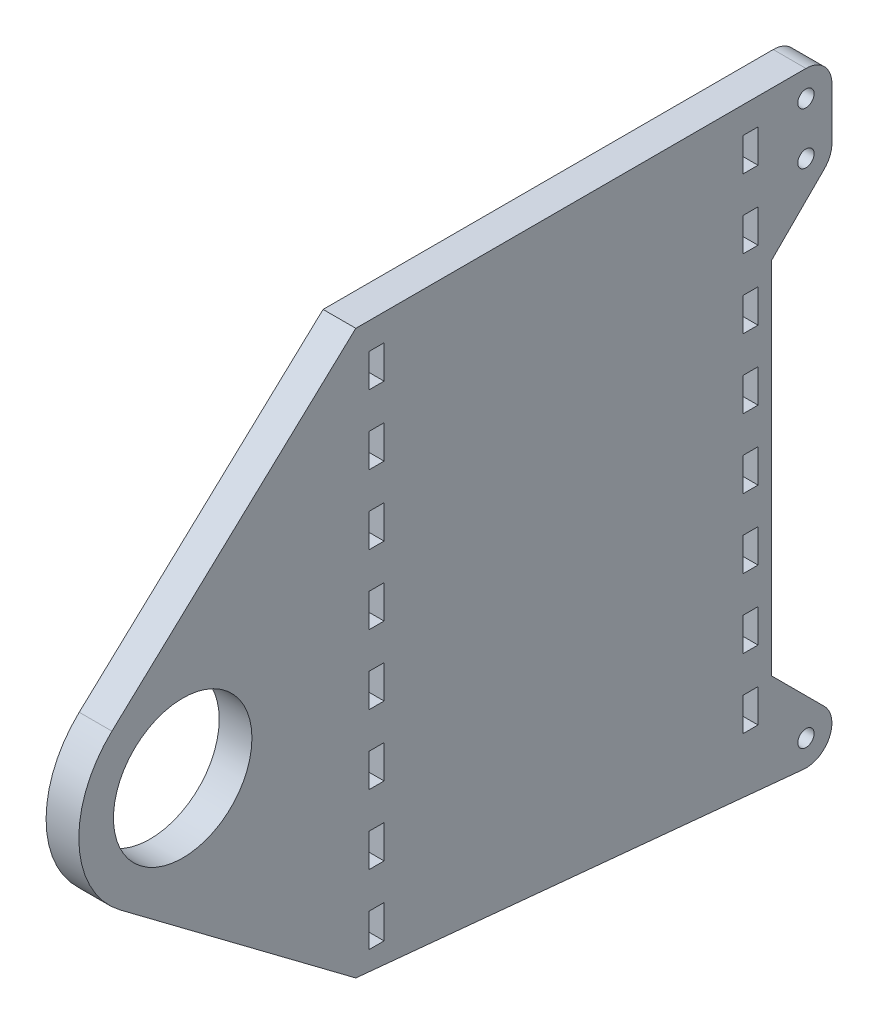
SolidWorks part; units mm, degrees
ref_plane "Front Plane" through (0, 0, 0) normal (0, 0, 1) x (1, 0, 0)
ref_plane "Top Plane" through (0, 0, 0) normal (0, 1, 0) x (1, 0, 0)
ref_plane "Right Plane" through (0, 0, 0) normal (1, 0, 0) x (0, 0, -1)
sketch "PlateGeometry" plane through (0, 0, 0) normal (1, 0, 0) x (0, 0, -1)
  line L1 (-38.1, -76.2) -> (38.1, -76.2) construction
  line L2 (-38.1, -76.2) -> (-38.1, 76.2) construction
  line L3 (-38.1, 76.2) -> (38.1, 76.2) construction
  line L4 (38.1, -76.2) -> (38.1, 76.2) construction
  line L5 (-38.1, -76.2) -> (38.1, 76.2) construction
  line L6 (-38.1, 76.2) -> (38.1, -76.2) construction
  line L11 (31.75, 76.2) -> (-31.75, 76.2) construction
  line L12 (31.75, 76.2) -> (31.75, -76.2) construction
  line L13 (31.75, -76.2) -> (-31.75, -76.2) construction
  line L14 (-31.75, 76.2) -> (-31.75, -76.2) construction
  line L15 (31.75, 76.2) -> (-31.75, -76.2) construction
  line L16 (31.75, -76.2) -> (-31.75, 76.2) construction
  point P0 (0, 0)
  point P9 (0, 0)
  line B0 (-35.7923, -66.6761) -> (-32.7923, -66.6739)
  line B1 (-35.7923, -66.6761) -> (-35.7877, -73.0261)
  line B2 (-35.7877, -73.0261) -> (-32.7877, -73.0239)
  line B3 (-32.7923, -66.6739) -> (-32.7877, -73.0239)
  line B4 (-35.7923, -66.6761) -> (-32.7877, -73.0239) construction
  line B5 (-35.7877, -73.0261) -> (-32.7923, -66.6739) construction
  line B6 (-35.7923, -53.9761) -> (-32.7923, -53.9739)
  line B7 (-35.7923, -53.9761) -> (-35.7877, -60.3261)
  line B8 (-35.7877, -60.3261) -> (-32.7877, -60.3239)
  line B9 (-32.7923, -53.9739) -> (-32.7877, -60.3239)
  line B10 (-35.7877, -60.3261) -> (-32.7923, -53.9739) construction
  line B11 (-35.7923, -41.2761) -> (-32.7923, -41.2739)
  line B12 (-35.7923, -41.2761) -> (-35.7877, -47.6261)
  line B13 (-35.7877, -47.6261) -> (-32.7877, -47.6239)
  line B14 (-32.7923, -41.2739) -> (-32.7877, -47.6239)
  line B15 (-35.7923, -41.2761) -> (-32.7877, -47.6239) construction
  line B16 (-35.7877, -47.6261) -> (-32.7923, -41.2739) construction
  line B17 (-35.7923, -28.5761) -> (-32.7923, -28.5739)
  line B18 (-35.7877, -34.9261) -> (-32.7877, -34.9239)
  line B19 (-32.7923, -28.5739) -> (-32.7877, -34.9239)
  line B20 (-35.7923, -15.8761) -> (-35.7877, -22.2261)
  line B21 (-32.7923, -15.8739) -> (-32.7877, -22.2239)
  line B22 (-35.7923, 9.5239) -> (-32.7923, 9.5261)
  line B23 (-32.7923, 9.5261) -> (-32.7877, 3.1761)
  line B24 (-35.7923, 9.5239) -> (-32.7877, 3.1761) construction
  line B25 (-35.7923, 22.2239) -> (-35.7877, 15.8739)
  line B26 (-35.7923, 34.9239) -> (-35.7877, 28.5739)
  line B27 (-35.7923, 47.6239) -> (-35.7877, 41.2739)
  line B28 (-35.7877, 41.2739) -> (-32.7923, 47.6261) construction
  line B29 (32.7886, -66.6757) -> (32.7914, -73.0257)
  line B30 (32.7914, -73.0257) -> (35.7914, -73.0243)
  line B31 (35.7886, -66.6743) -> (35.7914, -73.0243)
  line B32 (32.7886, -66.6757) -> (35.7914, -73.0243) construction
  line B33 (32.7914, -73.0257) -> (35.7886, -66.6743) construction
  line B34 (32.7886, -53.9757) -> (35.7886, -53.9743)
  line B35 (35.7886, -53.9743) -> (35.7914, -60.3243)
  line B36 (32.7914, -47.6257) -> (35.7914, -47.6243)
  line B37 (35.7886, -41.2743) -> (35.7914, -47.6243)
  line B38 (32.7886, -41.2757) -> (35.7914, -47.6243) construction
  line B39 (32.7886, -28.5757) -> (35.7914, -34.9243) construction
  line B40 (32.7886, -15.8757) -> (32.7914, -22.2257)
  line B41 (32.7886, -3.1757) -> (35.7914, -9.5243) construction
  line B42 (32.7914, -9.5257) -> (35.7886, -3.1743) construction
  line B43 (32.7886, 9.5243) -> (35.7886, 9.5257)
  line B44 (32.7886, 9.5243) -> (32.7914, 3.1743)
  line B45 (32.7914, 3.1743) -> (35.7914, 3.1757)
  line B46 (32.7886, 9.5243) -> (35.7914, 3.1757) construction
  line B47 (32.7886, 22.2243) -> (32.7914, 15.8743)
  line B48 (35.7886, 22.2257) -> (35.7914, 15.8757)
  line B49 (32.7886, 22.2243) -> (35.7914, 15.8757) construction
  line B50 (32.7914, 15.8743) -> (35.7886, 22.2257) construction
  line B51 (32.7914, 41.2743) -> (35.7914, 41.2757)
  line B52 (35.7886, 47.6257) -> (35.7914, 41.2757)
  line B53 (32.7886, 60.3243) -> (32.7914, 53.9743)
  line B54 (35.7886, 60.3257) -> (35.7914, 53.9757)
  line B55 (32.7886, 73.0243) -> (32.7914, 66.6743)
  line B56 (35.7886, 73.0257) -> (35.7914, 66.6757)
  line B57 (32.7914, 66.6743) -> (35.7886, 73.0257) construction
  circle B58 centre (-37.3063, -73.025) radius 5.5563 construction
  circle B59 centre (-37.3063, -73.025) radius 6.8263 construction
  circle B60 centre (-44.9262, -53.975) radius 5.5563 construction
  circle B61 centre (-44.9262, -53.975) radius 6.8263 construction
  dimension "D11" = 63.5
  dimension "D12" = 3.175
  dimension "D1" = 76.2
  dimension "D2" = 152.4
  dimension "D4" = 3.81
  dimension "D5" = 6.35
  dimension "D6" = 12.7
  dimension "D7" = 6.35
  dimension "D8" = 3.81
  dimension "D10" = 12.7
  dimension "D13" = 19.05
  dimension "D14" = 7.62
  dimension "D3" = 12
  dimension "D9" = 12
sketch_block_instance "SlotOutline-1"
sketch_block "SlotOutline" parameters "D1"=18.06, "D2"=7.2935
sketch_block_instance "SlotOutline-2"
sketch_block_instance "SlotOutline-3"
sketch_block_instance "SlotOutline-4"
sketch_block_instance "SlotOutline-5"
sketch_block_instance "SlotOutline-6"
sketch_block_instance "SlotOutline-7"
sketch_block_instance "SlotOutline-8"
sketch_block_instance "SlotOutline-9"
sketch_block_instance "SlotOutline-10"
sketch_block_instance "SlotOutline-11"
sketch_block_instance "SlotOutline-12"
sketch_block_instance "SlotOutline-13"
sketch_block_instance "SlotOutline-14"
sketch_block_instance "SlotOutline-15"
sketch_block_instance "SlotOutline-16"
sketch_block_instance "SlotOutline-17"
sketch_block_instance "SlotOutline-18"
sketch_block_instance "SlotOutline-19"
sketch_block_instance "SlotOutline-20"
sketch_block_instance "SlotOutline-21"
sketch_block_instance "SlotOutline-22"
sketch_block_instance "SlotOutline-23"
sketch_block_instance "SlotOutline-24"
sketch_block_instance "PulleyOutline-1"
sketch_block "PulleyOutline" parameters "D1"=11.1125, "D2"=13.6525
sketch_block_instance "PulleyOutline-2"
sketch "MotorGeometry" plane through (0, 0, 0) normal (1, 0, 0) x (0, 0, -1)
  line L0 (-83.2734, 1.775) -> (-83.2734, 49.025) construction
  line L3 (-50.2786, -55.4665) -> (-63.8121, -13.9087) construction
  line L4 (-41.2645, -76.9242) -> (-75.3216, -19.0975) construction
  line L5 (-38.1, -76.2) -> (-38.1, 76.2) construction
  line L6 (-38.1, -76.2) -> (38.1, -76.2) construction
  line L7 (38.1, -76.2) -> (38.1, 76.2) construction
  line L8 (-83.2734, 17.65) -> (-69.85, 9.9) construction
  line L9 (-69.85, 9.9) -> (-56.4266, 17.65) construction
  line L10 (-56.4266, 17.65) -> (-56.4266, 33.15) construction
  line L11 (-56.4266, 33.15) -> (-69.85, 40.9) construction
  line L12 (-69.85, 40.9) -> (-83.2734, 33.15) construction
  line L13 (-83.2734, 33.15) -> (-83.2734, 17.65) construction
  line L14 (-86.2734, 1.775) -> (-86.2734, 49.025)
  line L15 (-80.2734, 1.775) -> (-80.2734, 49.025)
  line L16 (-56.4266, 1.775) -> (-56.4266, 49.025) construction
  line L17 (-59.4266, 1.775) -> (-59.4266, 49.025)
  line L18 (-53.4266, 1.775) -> (-53.4266, 49.025)
  line L19 (-69.85, 8.3125) -> (-69.85, 47.25) construction
  line L20 (-72.85, 8.3125) -> (-72.85, 47.25)
  line L21 (-66.85, 8.3125) -> (-66.85, 47.25)
  circle A0 centre (44.45, -66.675) radius 1.5
  circle A1 centre (-69.85, -15.875) radius 11
  circle A5 centre (-69.85, -15.875) radius 30 construction
  circle A6 centre (-69.85, -15.875) radius 6.35 construction
  circle A7 centre (-44.9262, -53.975) radius 5.5562 construction
  circle A8 centre (-37.3063, -73.025) radius 5.5562 construction
  circle A9 centre (-69.85, -15.875) radius 25.5 construction
  circle A10 centre (-69.85, 25.4) radius 16 construction
  circle A11 centre (-69.85, 25.4) radius 11.5 construction
  circle A12 centre (-69.85, 25.4) radius 13.4234 construction
  arc A13 (-86.2734, 1.775) -> (-80.2734, 1.775) centre (-83.2734, 1.775) ccw
  arc A14 (-80.2734, 49.025) -> (-86.2734, 49.025) centre (-83.2734, 49.025) ccw
  arc A15 (-59.4266, 1.775) -> (-53.4266, 1.775) centre (-56.4266, 1.775) ccw
  arc A16 (-53.4266, 49.025) -> (-59.4266, 49.025) centre (-56.4266, 49.025) ccw
  arc A17 (-72.85, 8.3125) -> (-66.85, 8.3125) centre (-69.85, 8.3125) ccw
  arc A18 (-66.85, 47.25) -> (-72.85, 47.25) centre (-69.85, 47.25) ccw
  point P29 (-83.2734, 25.4)
  point P39 (-56.4266, 25.4)
  point P46 (-69.85, 27.7812)
  dimension "D1" = 22
  dimension "D4" = 60
  dimension "D5" = 12.7
  dimension "D7" = 4.5
  dimension "D8" = 32
  dimension "D9" = 4.5
  dimension "D13" = 3
  dimension "D3" = 6
  dimension "D2" = 31
  dimension "D6" = 38.1
  dimension "D10" = 31.75
  dimension "D11" = 9.525
  dimension "D12" = 6.35
  dimension "D14" = 15.875
  dimension "D15" = 1.5875
  dimension "D16" = 15.875
  dimension "D17" = 6.35
  dimension "D18" = 41.275
sketch "Sketch4" plane through (0, 0, 0) normal (1, 0, 0) x (0, 0, -1)
  line L0 (49.2125, 25.4) -> (49.2125, 34.925)
  line L1 (47.8176, 22.0324) -> (38.1, 12.3148)
  line L2 (-30.48, -50.8) -> (-38.1, -50.8) construction
  line L3 (-30.48, -50.8) -> (-30.48, -63.5) construction
  line L4 (-30.48, -63.5) -> (-38.1, -63.5) construction
  line L5 (-38.1, -50.8) -> (-38.1, -63.5) construction
  line L6 (-30.48, -50.8) -> (-38.1, -63.5) construction
  line L7 (-30.48, -63.5) -> (-38.1, -50.8) construction
  line L8 (38.1, 12.3148) -> (38.1, -53.5898)
  line L9 (38.1, -53.5898) -> (47.8176, -63.3074)
  line L10 (38.1, -76.2) -> (38.1, 76.2) construction
  line L11 (43.9929, -71.4155) -> (-38.1, -63.5)
  line L12 (-38.1, -63.5) -> (-81.28, -31.115)
  line L13 (-82.8266, -1.9283) -> (-38.1, 39.6875)
  line L14 (-38.1, -76.2) -> (-38.1, 76.2) construction
  line L15 (-38.1, 39.6875) -> (44.45, 39.6875)
  line L17 (-83.2734, 1.775) -> (-83.2734, 58.55) construction
  line L18 (-86.2734, 1.775) -> (-86.2734, 58.55) construction
  line L19 (-80.2734, 1.775) -> (-80.2734, 58.55) construction
  line L20 (-69.85, 8.3125) -> (-69.85, 53.6) construction
  line L21 (-72.85, 8.3125) -> (-72.85, 53.6) construction
  line L22 (-66.85, 8.3125) -> (-66.85, 53.6) construction
  line L23 (-56.4266, 1.775) -> (-56.4266, 58.55) construction
  line L24 (-59.4266, 1.775) -> (-59.4266, 58.55) construction
  line L25 (-53.4266, 1.775) -> (-53.4266, 58.55) construction
  circle A0 centre (44.45, 25.4) radius 1.5
  circle A1 centre (44.45, 34.925) radius 1.5
  circle A2 centre (44.45, -66.675) radius 4.7625 construction
  circle A3 centre (44.45, 25.4) radius 4.7625 construction
  circle A4 centre (44.45, 34.925) radius 4.7625 construction
  circle A5 centre (-69.85, -15.875) radius 12.7
  arc A6 (43.9929, -71.4155) -> (47.8176, -63.3074) centre (44.45, -66.675) ccw
  circle A7 centre (-69.85, -15.875) radius 19.05
  arc A8 (47.8176, 22.0324) -> (49.2125, 25.4) centre (44.45, 25.4) ccw
  arc A9 (49.2125, 34.925) -> (44.45, 39.6875) centre (44.45, 34.925) ccw
  circle A10 centre (44.45, -66.675) radius 1.5
  arc A11 (-86.2734, 1.775) -> (-80.2734, 1.775) centre (-83.2734, 1.775) ccw construction
  arc A12 (-80.2734, 58.55) -> (-86.2734, 58.55) centre (-83.2734, 58.55) ccw construction
  arc A13 (-72.85, 8.3125) -> (-66.85, 8.3125) centre (-69.85, 8.3125) ccw construction
  arc A14 (-66.85, 53.6) -> (-72.85, 53.6) centre (-69.85, 53.6) ccw construction
  arc A15 (-59.4266, 1.775) -> (-53.4266, 1.775) centre (-56.4266, 1.775) ccw construction
  arc A16 (-53.4266, 58.55) -> (-59.4266, 58.55) centre (-56.4266, 58.55) ccw construction
  arc A17 (-72.85, 24.1875) -> (-66.85, 24.1875) centre (-69.85, 24.1875) cw construction
  arc A18 (-72.85, 33.3625) -> (-66.85, 33.3625) centre (-69.85, 33.3625) ccw construction
  point P12 (-34.29, -57.15)
  point P36 (-83.2734, 30.1625)
  point P47 (-69.85, 30.9562)
  point P55 (-56.4266, 30.1625)
  dimension "D1" = 3
  dimension "D4" = 9.525
  dimension "D9" = 25.4
  dimension "D10" = 38.1
  dimension "D11" = 6
  dimension "D14" = 3.175
  dimension "D2" = 9.525
  dimension "D3" = 101.6
  dimension "D5" = 3.81
  dimension "D6" = 12.7
  dimension "D7" = 45
  dimension "D8" = 45
  dimension "D12" = 12.7
  dimension "D13" = 25.4
  dimension "D15" = 15.875
extrude "Boss-Extrude1" add sketch "Sketch4" along normal mid plane 6 contours L0 A9 L13 A7 L12 L11 A6 L9 L8 L1 A8 A0 A1 | A7 A5 | L24 A15 L25 L13 | L13 A13 L22 region at (0, -13.1889, 7.3945) region at (0, 1.0968, 62.4593)
sketch "Sketch5" plane through (3, 0, 0) normal (1, 0, 0) x (0, 0, -1)
  point P0 (5.4404, -51.7245)
  line B0 (35.665, -54.102) -> (32.915, -54.102)
  line B1 (35.665, -54.102) -> (35.665, -60.198)
  line B2 (35.665, -60.198) -> (32.915, -60.198)
  line B3 (32.915, -54.102) -> (32.915, -60.198)
  line B4 (35.665, -54.102) -> (32.915, -60.198) construction
  line B5 (35.665, -60.198) -> (32.915, -54.102) construction
  line B6 (-32.915, -54.102) -> (-35.665, -54.102)
  line B7 (-32.915, -54.102) -> (-32.915, -60.198)
  line B8 (-32.915, -60.198) -> (-35.665, -60.198)
  line B9 (-35.665, -54.102) -> (-35.665, -60.198)
  line B10 (-32.915, -54.102) -> (-35.665, -60.198) construction
  line B11 (-32.915, -60.198) -> (-35.665, -54.102) construction
sketch_block_instance "Slot-1"
sketch_block "Slot" parameters "D1"=11.2845, "D2"=5.6739
sketch_block_instance "Slot-2"
extrude "LowerSlot" cut sketch "Sketch5" against normal through all both and the other way through all contours B0 B3 B2 B1 region at (3, -57.15, -34.29)
extrude "UpperSlot" cut sketch "Sketch5<3>" against normal through all both and the other way through all contours B6 B9 B8 B7 region at (3, -57.15, 34.29)
sketch "Sketch5<3>" plane through (3, 0, 0) normal (1, 0, 0) x (0, 0, -1) same geometry as "Sketch5"
pattern_linear "LowerSlots" count 8 spacing 12.7 along (0, 1, 0) of "LowerSlot"
pattern_linear "UpperSlots" count 8 spacing 12.7 along (0, 1, 0) of "UpperSlot"
